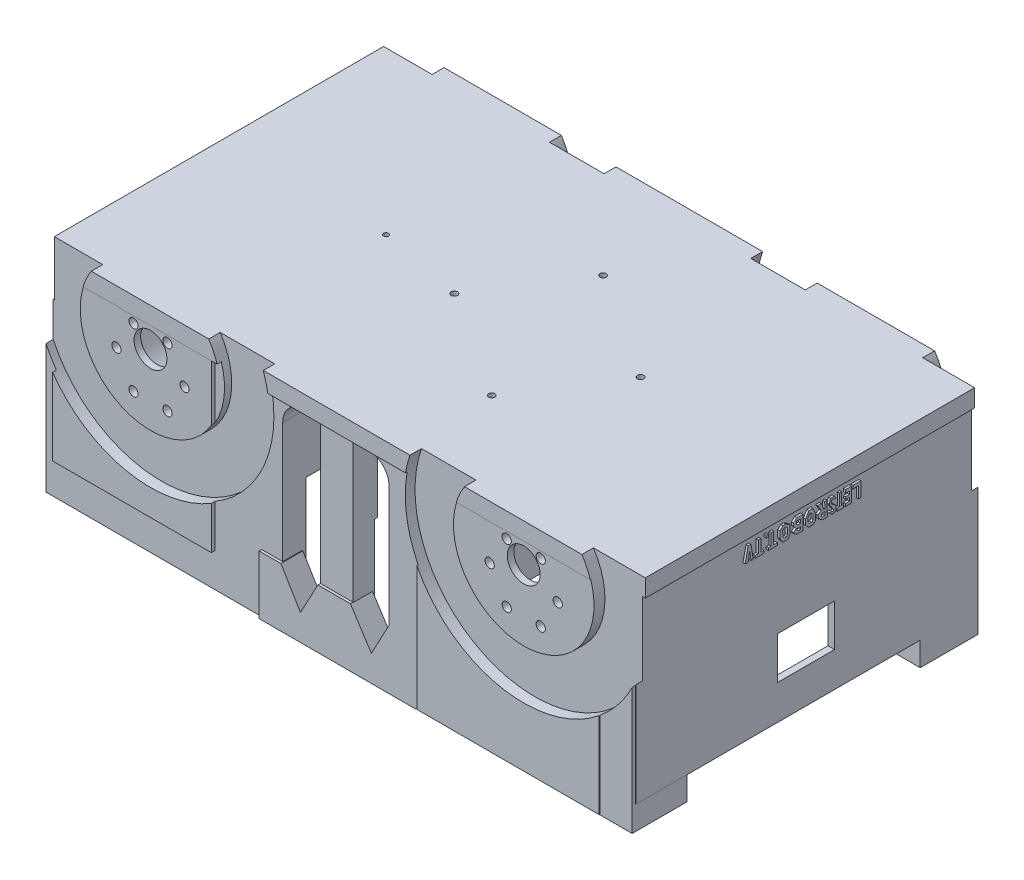
SolidWorks part; units mm, degrees
ref_plane "Front Plane" through (0, 0, 0) normal (0, 0, 1) x (1, 0, 0)
ref_plane "Top Plane" through (0, 0, 0) normal (0, 1, 0) x (1, 0, 0)
ref_plane "Right Plane" through (0, 0, 0) normal (1, 0, 0) x (0, 0, -1)
sketch "MotorHoldersSketch" plane through (0, 0, 0) normal (0, 0, 1) x (1, 0, 0)
  line L0 (0, 0) -> (170, 0) construction
  line L1 (0, 0) -> (0, 23.41) construction
  line L2 (170, 0) -> (170, 23.41) construction
  circle A0 centre (0, 0) radius 23.41
  circle A1 centre (170, 0) radius 23.41
ref_axis "MotorCenterAxis1" through (0, 0, 0) along (0, 0, 1)
ref_axis "MotorCenterAxis2" through (170, 0, 0) along (0, 0, 1)
extrude "MotorHolders" add sketch "MotorHoldersSketch" along normal blind 80 and the other way blind 80
sketch "Sketch3" plane through (0, 0, 0) normal (0, 0, 1) x (1, 0, 0)
  line L1 (1.9406, 21.133) -> (168.3435, 21.133)
  line L2 (1.9406, 21.133) -> (1.9406, 18.3155)
  line L3 (1.9406, 18.3155) -> (168.3435, 18.3155)
  line L4 (168.3435, 21.133) -> (168.3435, 18.3155)
sketch "Sketch4" plane through (0, 0, 0) normal (0, 1, 0) x (1, 0, 0)
  line L1 (221.2811, -76.3794) -> (-41.4939, -76.3794)
  line L2 (221.2811, -76.3794) -> (221.2811, 76.7331)
  line L3 (221.2811, 76.7331) -> (-41.4939, 76.7331)
  line L4 (-41.4939, -76.3794) -> (-41.4939, 76.7331)
extrude "Cut-Extrude1" cut sketch "Sketch4" against normal blind 26
ref_axis "Axis3" through (170, 0, 0) along (0, -1, 0)
sketch3d "ReferencePlanePosition"
  line L0 (170, 0, 0) -> (170, -34.8293, 0)
  line L1 (170, 0, 0) -> (170, -38.994, 0) construction
ref_plane "ReferencePlane" through (170, -34.8293, 0) normal (0, -1, 0) x (-1, 0, 0)
sketch "Sketch6" plane through (170, -34.8293, 0) normal (0, -1, 0) x (-1, 0, 0)
  line L1 (219.5858, 78.949) -> (112.1002, 78.949)
  line L2 (219.5858, 78.949) -> (219.5858, 65.5282)
  line L3 (219.5858, 65.5282) -> (112.1002, 65.5282)
  line L4 (112.1002, 78.949) -> (112.1002, 65.5282)
  line L5 (219.3147, -40.0209) -> (111.499, -40.0209)
  line L6 (219.3147, -40.0209) -> (219.3147, -78.2822)
  line L7 (219.3147, -78.2822) -> (111.499, -78.2822)
  line L8 (111.499, -40.0209) -> (111.499, -78.2822)
  line L9 (61.4891, 77.8627) -> (19.9904, 77.8627)
  line L10 (61.4891, 77.8627) -> (61.4891, 40.7512)
  line L11 (61.4891, 40.7512) -> (19.9904, 40.7512)
  line L12 (19.9904, 77.8627) -> (19.9904, 40.7512)
  line L13 (61.8484, -44.1716) -> (20.0852, -44.1716)
  line L14 (61.8484, -44.1716) -> (61.8484, -79.4437)
  line L15 (61.8484, -79.4437) -> (20.0852, -79.4437)
  line L16 (20.0852, -44.1716) -> (20.0852, -79.4437)
  line L17 (213.765, 73.0364) -> (192.9548, 73.0364)
  line L18 (213.765, 73.0364) -> (213.765, 71.0153)
  line L19 (213.765, 71.0153) -> (192.9548, 71.0153)
  line L20 (192.9548, 73.0364) -> (192.9548, 71.0153)
  line L21 (41.3552, 69.1777) -> (28.5109, 69.1777)
  line L22 (41.3552, 69.1777) -> (41.3552, 50.8413)
  line L23 (41.3552, 50.8413) -> (28.5109, 50.8413)
  line L24 (28.5109, 69.1777) -> (28.5109, 50.8413)
  line L25 (43.3068, -72.8101) -> (32.1723, -72.8101)
  line L26 (43.3068, -72.8101) -> (43.3068, -54.7747)
  line L27 (43.3068, -54.7747) -> (32.1723, -54.7747)
  line L28 (32.1723, -72.8101) -> (32.1723, -54.7747)
  line L29 (211.9411, -70.4881) -> (201.0982, -70.4881)
  line L30 (211.9411, -70.4881) -> (211.9411, -60.1404)
  line L31 (211.9411, -60.1404) -> (201.0982, -60.1404)
  line L32 (201.0982, -70.4881) -> (201.0982, -60.1404)
  line L33 (97.1795, 78.949) -> (79.4162, 78.949)
  line L34 (97.1795, 78.949) -> (97.1795, 67.7632)
  line L35 (97.1795, 67.7632) -> (79.4162, 67.7632)
  line L36 (79.4162, 78.949) -> (79.4162, 67.7632)
  line L37 (58.6711, 51.3198) -> (53.8697, 51.3198)
  line L38 (58.6711, 51.3198) -> (58.6711, 67.7632)
  line L39 (58.6711, 67.7632) -> (53.8697, 67.7632)
  line L40 (53.8697, 51.3198) -> (53.8697, 67.7632)
  line L41 (94.2281, -78.2822) -> (79.4162, -78.2822)
  line L42 (94.2281, -78.2822) -> (94.2281, -67.2515)
  line L43 (94.2281, -67.2515) -> (79.4162, -67.2515)
  line L44 (79.4162, -78.2822) -> (79.4162, -67.2515)
  line L45 (56.3648, -69.8638) -> (51.7107, -69.8638)
  line L46 (56.3648, -69.8638) -> (56.3648, -55.4273)
  line L47 (56.3648, -55.4273) -> (51.7107, -55.4273)
  line L48 (51.7107, -69.8638) -> (51.7107, -55.4273)
  line L49 (-20.7001, -79.4437) -> (-48.8506, -79.4437)
  line L50 (-20.7001, -79.4437) -> (-20.7001, -54.5097)
  line L51 (-20.7001, -54.5097) -> (-48.8506, -54.5097)
  line L52 (-48.8506, -79.4437) -> (-48.8506, -54.5097)
  line L53 (-18.3873, 77.8627) -> (-49.0581, 77.8627)
  line L54 (-18.3873, 77.8627) -> (-18.3873, 51.5325)
  line L55 (-18.3873, 51.5325) -> (-49.0581, 51.5325)
  line L56 (-49.0581, 77.8627) -> (-49.0581, 51.5325)
  line L57 (-41.8141, -72.8101) -> (-31.6362, -72.8101)
  line L58 (-41.8141, -72.8101) -> (-41.8141, -62.9794)
  line L59 (-41.8141, -62.9794) -> (-31.6362, -62.9794)
  line L60 (-31.6362, -72.8101) -> (-31.6362, -62.9794)
  line L61 (-31.6362, 69.1777) -> (-41.5347, 69.1777)
  line L62 (-31.6362, 69.1777) -> (-31.6362, 58.5421)
  line L63 (-31.6362, 58.5421) -> (-41.5347, 58.5421)
  line L64 (-41.5347, 69.1777) -> (-41.5347, 58.5421)
extrude "PowerBankHolders" add sketch "Sketch6" along normal blind 40 and the other way blind 59 separate body
sketch3d "3DSketch3"
  line L0 (170, 0, 0) -> (170, -64.5, 0) construction
ref_plane "Plane2" through (170, -64.5, 0) normal (0, -1, 0) x (-1, 0, 0)
sketch "Sketch7" plane through (170, -64.5, 0) normal (0, -1, 0) x (-1, 0, 0)
  line L1 (-9.5047, -80.801) -> (181.32, -80.801)
  line L2 (-9.5047, -80.801) -> (-9.5047, 73.8662)
  line L3 (-9.5047, 73.8662) -> (181.32, 73.8662)
  line L4 (181.32, -80.801) -> (181.32, 73.8662)
  line L5 (151.8712, -54.3972) -> (26.5361, -54.3972)
  line L6 (151.8712, -54.3972) -> (151.8712, 46.2413)
  line L7 (151.8712, 46.2413) -> (26.5361, 46.2413)
  line L8 (26.5361, -54.3972) -> (26.5361, 46.2413)
ref_point "Point1"
ref_point "Point2"
sketch3d "3DSketch11"
  line L0 (0, 0, -80) -> (170, 0, 80) construction
  point P4 (85, 0, 0)
sketch "MotorHolderExtrudeSketch" plane through (0, 0, 0) normal (0, 0, 1) x (1, 0, 0)
  circle A0 centre (170, 0) radius 20.415
  circle A1 centre (0, 0) radius 20.415
  circle A3 centre (0, 0) radius 23.41 construction
  circle A4 centre (170, 0) radius 23.41 construction
ref_point "TopOfMotors"
ref_plane "TangentToTopOfMotors" through (0, -20.415, 0) normal (0, 1, 0) x (1, 0, 0)
ref_axis "Axis4" through (85, 0, 0) along (0, -1, 0)
ref_plane "BottomOfPowerBankRegion" through (0, -20.425, 0) normal (0, 1, 0) x (1, 0, 0)
ref_point "CenterAtBottomOfPowerBank"
ref_plane "TopOfPowerBankPlane" through (0, -54.425, 0) normal (0, 1, 0) x (1, 0, 0)
sketch "Sketch13" plane through (0, -54.425, 0) normal (0, 1, 0) x (1, 0, 0)
  line L1 (-19.4498, 72.5454) -> (166.1636, 72.5454)
  line L2 (-19.4498, 72.5454) -> (-19.4498, -78.2051)
  line L3 (-19.4498, -78.2051) -> (166.1636, -78.2051)
  line L4 (166.1636, 72.5454) -> (166.1636, -78.2051)
  line L5 (19.3173, -49.583) -> (137.9607, -49.583)
  line L6 (19.3173, -49.583) -> (19.3173, -21.0549)
  line L7 (19.3173, -21.0549) -> (137.9607, -21.0549)
  line L8 (137.9607, -49.583) -> (137.9607, -21.0549)
  line L9 (19.3173, 56.6778) -> (137.9607, 56.6778)
  line L10 (19.3173, 56.6778) -> (19.3173, 36.3234)
  line L11 (19.3173, 36.3234) -> (137.9607, 36.3234)
  line L12 (137.9607, 56.6778) -> (137.9607, 36.3234)
  line L13 (19.3173, 18.3186) -> (137.9607, 18.3186)
  line L14 (19.3173, 18.3186) -> (19.3173, -7.3615)
  line L15 (19.3173, -7.3615) -> (137.9607, -7.3615)
  line L16 (137.9607, 18.3186) -> (137.9607, -7.3615)
sketch "Sketch15" plane through (150.0096, 0, 0) normal (1, 0, 0) x (0, 0, -1)
  line L1 (72.5313, -25.7765) -> (45.7099, -25.7765)
  line L2 (72.5313, -25.7765) -> (72.5313, -24.2242)
  line L3 (72.5313, -24.2242) -> (45.7099, -24.2242)
  line L4 (45.7099, -25.7765) -> (45.7099, -24.2242)
ref_plane "Plane6" through (0, 0, 0) normal (0, 0, 1) x (1, 0, 0)
sketch "MotorGeometry1" plane through (0, 0, 0) normal (0, 0, 1) x (1, 0, 0)
  line L0 (170, 0) -> (170, -13.42)
  line L1 (170, 0) -> (170, -34.8293) construction
  line L2 (170, -13.42) -> (162.25, -13.42) construction
  line L3 (170, -13.42) -> (177.75, -13.42) construction
  line L4 (170, -13.42) -> (170, 7) construction
  line L5 (170, 0) -> (185.5, 0) construction
  line L6 (170, 0) -> (154.5, 0) construction
  line L7 (170, 0) -> (170, 13.42) construction
  line L8 (170, 0) -> (170, 23.41) construction
  line L9 (170, 13.42) -> (177.75, 13.42) construction
  line L10 (170, 13.42) -> (162.25, 13.42)
ref_axis "BoltAxisA" through (185.5, 0, 0) along (0, 0, 1)
ref_axis "BoltAxisB" through (177.75, -13.42, 0) along (0, 0, 1)
ref_axis "BoltAxisC" through (162.25, -13.42, 0) along (0, 0, 1)
ref_axis "BoltAxisD" through (154.5, 0, 0) along (0, 0, 1)
ref_axis "BoltAxisE" through (162.25, 13.42, 0) along (0, 0, 1)
ref_axis "BoltAxisF" through (177.75, 13.42, 0) along (0, 0, 1)
ref_point "Point6"
ref_point "Point7"
ref_point "Point8"
ref_point "Point9"
ref_point "Point10"
ref_point "Point11"
ref_point "Point12"
ref_point "Point13"
ref_point "Point14"
ref_point "Point15"
ref_point "Point16"
ref_point "Point17"
ref_plane "Plane7" through (0, 0, 0) normal (0, 0, 1) x (1, 0, 0)
sketch "MotorGeometry2" plane through (0, 0, 0) normal (0, 0, 1) x (1, 0, 0)
  line L0 (0, 0) -> (0, -13.42) construction
  line L1 (0, -13.42) -> (7.75, -13.42) construction
  line L2 (0, -13.42) -> (-7.75, -13.42) construction
  line L3 (0, 0) -> (0, 13.42)
  line L4 (0, -13.42) -> (0, 7) construction
  line L5 (0, 13.42) -> (7.75, 13.42) construction
  line L6 (0, 13.42) -> (-7.75, 13.42) construction
  line L7 (0, 0) -> (15.5, 0) construction
  line L8 (0, 0) -> (-15.5, 0) construction
  line L9 (0, 0) -> (0, 23.41) construction
ref_axis "Axis11" through (15.5, 0, 0) along (0, 0, 1)
ref_axis "Axis12" through (7.75, 13.42, 0) along (0, 0, 1)
ref_axis "Axis13" through (-7.75, 13.42, 0) along (0, 0, 1)
ref_axis "Axis14" through (-15.5, 0, 0) along (0, 0, 1)
ref_axis "Axis15" through (-7.75, -13.42, 0) along (0, 0, 1)
ref_axis "Axis16" through (7.75, -13.42, 0) along (0, 0, 1)
ref_point "Point18"
ref_point "Point19"
ref_point "Point20"
ref_point "Point21"
ref_point "Point22"
ref_point "Point23"
ref_point "Point24"
ref_point "Point25"
ref_point "Point26"
ref_point "Point27"
ref_point "Point28"
ref_point "Point29"
ref_plane "BottomPlane" through (0, 19.575, 0) normal (0, 1, 0) x (1, 0, 0)
ref_axis "OutputShaftReference1" through (0, 7, 0) along (0, 0, 1)
ref_point "Point35"
ref_axis "OutputShaftReference2" through (170, 7, 0) along (0, 0, 1)
sketch "Sketch21" plane through (0, 19.575, 0) normal (0, 1, 0) x (1, 0, 0)
  line L0 (219.6842, -79.5488) -> (-50.341, -79.5488) construction
  line L1 (-50.341, -79.5488) -> (-50.341, 79.7899) construction
  line L2 (-50.341, 79.7899) -> (219.6842, 79.7899) construction
  line L3 (219.6842, 79.7899) -> (219.6842, -79.5488) construction
  circle A0 centre (85, 0) radius 156.3953
extrude "BottomPlate" add sketch "Sketch21" along normal blind 5 and the other way blind 3
ref_plane "HoleReferencePlane1" through (0, 0, 80) normal (0, 0, 1) x (1, 0, 0)
ref_point "OutputShaftPosition3"
ref_point "OutputShaftPosition1"
sketch "Sketch23" plane through (0, 0, 80) normal (0, 0, 1) x (1, 0, 0)
  line L1 (27.7411, -59.3229) -> (-44.5901, -59.3229)
  line L2 (27.7411, -59.3229) -> (27.7411, 21.8402)
  line L3 (27.7411, 21.8402) -> (-44.5901, 21.8402)
  line L4 (-44.5901, -59.3229) -> (-44.5901, 21.8402)
  line L5 (121.3218, 21.8402) -> (204.258, 21.8402)
  line L6 (121.3218, 21.8402) -> (121.3218, -74.371)
  line L7 (121.3218, -74.371) -> (204.258, -74.371)
  line L8 (204.258, 21.8402) -> (204.258, -74.371)
extrude "MotorMountingSupport1" add sketch "Sketch23" against normal blind 6
ref_plane "HoleReferencePlane2" through (0, 0, -80) normal (0, 0, -1) x (-1, 0, 0)
ref_point "OutputShaftPosition4"
ref_point "OutputShaftPosition2"
sketch "Sketch24" plane through (0, 0, -80) normal (0, 0, -1) x (-1, 0, 0)
  line L1 (-202.1905, -75.2023) -> (-123.8485, -75.2023)
  line L2 (-202.1905, -75.2023) -> (-202.1905, 19.2374)
  line L3 (-202.1905, 19.2374) -> (-123.8485, 19.2374)
  line L4 (-123.8485, -75.2023) -> (-123.8485, 19.2374)
  line L5 (-24.3642, -64.1521) -> (29.5505, -64.1521)
  line L6 (-24.3642, -64.1521) -> (-24.3642, 22.5226)
  line L7 (-24.3642, 22.5226) -> (29.5505, 22.5226)
  line L8 (29.5505, -64.1521) -> (29.5505, 22.5226)
extrude "MotorMountingSuppor2" add sketch "Sketch24" against normal blind 6
sketch "Sketch17" plane through (0, 0, 80) normal (0, 0, 1) x (1, 0, 0)
  circle A0 centre (185.5, 0) radius 2.1
  circle A1 centre (177.75, -13.42) radius 2.1
  circle A2 centre (162.25, -13.42) radius 2.1
  circle A3 centre (154.5, 0) radius 2.1
  circle A4 centre (162.25, 13.42) radius 2.1
  circle A5 centre (177.75, 13.42) radius 2.1
  circle A6 centre (170, 7) radius 7.5
extrude "MotorHoles1" cut sketch "Sketch17" against normal blind 31.5
sketch "Sketch19" plane through (0, 0, -80) normal (0, 0, -1) x (-1, 0, 0)
  circle A0 centre (-185.5, 0) radius 2.1
  circle A1 centre (-177.75, -13.42) radius 2.1
  circle A2 centre (-162.25, -13.42) radius 2.1
  circle A3 centre (-154.5, 0) radius 2.1
  circle A4 centre (-162.25, 13.42) radius 2.1
  circle A5 centre (-177.75, 13.42) radius 2.1
  circle A6 centre (-170, 7) radius 7.5
sketch "BoltHolesSketch3" plane through (0, 0, 80) normal (0, 0, 1) x (1, 0, 0)
  circle A0 centre (7.75, -13.42) radius 2.1
  circle A1 centre (15.5, 0) radius 2.1
  circle A2 centre (7.75, 13.42) radius 2.1
  circle A3 centre (-7.75, 13.42) radius 2.1
  circle A4 centre (-15.5, 0) radius 2.1
  circle A5 centre (-7.75, -13.42) radius 2.1
  circle A6 centre (0, 7) radius 7.5
extrude "Cut-Extrude4" cut sketch "Sketch19" against normal blind 30
extrude "MotorHoles3" cut sketch "BoltHolesSketch3" against normal blind 31.5
sketch "BoltHolesSketch4" plane through (0, 0, -80) normal (0, 0, -1) x (-1, 0, 0)
  circle A0 centre (-15.5, 0) radius 2.1
  circle A1 centre (-7.75, 13.42) radius 2.1
  circle A2 centre (7.75, 13.42) radius 2.1
  circle A3 centre (15.5, 0) radius 2.1
  circle A4 centre (7.75, -13.42) radius 2.1
  circle A5 centre (-7.75, -13.42) radius 2.1
  circle A6 centre (0, 7) radius 7.5
extrude "MotorHoles4" cut sketch "BoltHolesSketch4" against normal blind 15
ref_plane "Front" through (219.0581, 0, 0) normal (1, 0, 0) x (0, 0, -1)
sketch "Sketch29" plane through (219.0581, 0, 0) normal (1, 0, 0) x (0, 0, -1)
  line L1 (76.6955, -63.9254) -> (-77.9397, -63.9254)
  line L2 (76.6955, -63.9254) -> (76.6955, 20.2062)
  line L3 (76.6955, 20.2062) -> (-77.9397, 20.2062)
  line L4 (-77.9397, -63.9254) -> (-77.9397, 20.2062)
  line L5 (-13.4507, -48.1531) -> (12.5493, -48.1531)
  line L6 (-13.4507, -48.1531) -> (-13.4507, -28.9404)
  line L7 (-13.4507, -28.9404) -> (12.5493, -28.9404)
  line L8 (12.5493, -48.1531) -> (12.5493, -28.9404)
extrude "Boss-Extrude8" add sketch "Sketch29" against normal blind 3
ref_plane "RaspberryPiBasePlane" through (0, 16.575, 0) normal (0, -1, 0) x (-1, 0, 0)
sketch "Sketch27" plane through (0, 16.575, 0) normal (0, -1, 0) x (-1, 0, 0)
  line L1 (31.6337, 64.5517) -> (-194.8264, 64.5517)
  line L2 (31.6337, 64.5517) -> (31.6337, -65.4335)
  line L3 (31.6337, -65.4335) -> (-194.8264, -65.4335)
  line L4 (-194.8264, 64.5517) -> (-194.8264, -65.4335)
extrude "Boss-Extrude6" add sketch "Sketch27" against normal blind 3
ref_plane "Plane12" through (0, -74.8293, 0) normal (0, -1, 0) x (-1, 0, 0)
sketch "Sketch28" plane through (0, -74.8293, 0) normal (0, -1, 0) x (-1, 0, 0)
  line L1 (-189.3897, -97.3973) -> (-123.0026, -97.3973)
  line L2 (-189.3897, -97.3973) -> (-189.3897, 96.7192)
  line L3 (-189.3897, 96.7192) -> (-123.0026, 96.7192)
  line L4 (-123.0026, -97.3973) -> (-123.0026, 96.7192)
sketch "Sketch40" plane through (0, 16.575, 0) normal (0, -1, 0) x (1, 0, 0)
  line L1 (-49.5858, -65.5282) -> (-15.7443, -65.5282)
  line L2 (-49.5858, -65.5282) -> (-49.5858, -33.9964)
  line L3 (-49.5858, -33.9964) -> (-15.7443, -33.9964)
  line L4 (-15.7443, -65.5282) -> (-15.7443, -33.9964)
extrude "Boss-Extrude11" add sketch "Sketch40" along normal blind 40
fillet "Fillet2" radius 15 1 edges at (-33.0588, 16.575, -33.9964) type face fillet first side face at (-28.7089, -2.1691, -33.9964) second side face at (85, 16.575, 156.3953)
fillet "Fillet3" radius 15 1 edges at (-32.6651, -23.425, -65.5282) type face fillet first side face at (-5.65, -13.42, -65.5282) second side face at (-32.6651, -23.425, -49.7623)
sketch "Sketch11" plane through (0, -20.425, 0) normal (0, 1, 0) x (1, 0, 0)
  line L0 (-34.2162, 4.2922) -> (204.2162, -4.2922) construction
  line L5 (-34.2162, -64.7581) -> (-34.2162, 73.3425)
  line L6 (204.2162, 63.611) -> (204.2162, -72.1954)
  line L7 (204.2162, -72.1954) -> (-34.2162, -64.7581)
  line L8 (204.2162, 63.611) -> (-34.2162, 73.3425)
  circle A0 centre (85, 0) radius 104 construction
extrude "PowerBankCut" cut sketch "Sketch11" against normal up to surface (54.4043 mm away) up to face at (204.7754, -74.8293, 66.9767)
extrude "MotorHolderCut" cut sketch "MotorHolderExtrudeSketch" against normal blind 77 and the other way blind 77
sketch "Sketch31" plane through (219.0581, 0, 0) normal (1, 0, 0) x (0, 0, -1)
  line L0 (-11.9853, 13.4398) -> (-13.3624, 12.0627)
  line L1 (-13.3624, 12.0627) -> (-13.3624, 8.9452)
  line L2 (-11.9853, 6.9748) -> (-13.3624, 8.9452)
  line L3 (23.5583, 6.7877) -> (23.5583, 13.4398)
  line L4 (23.5583, 13.4398) -> (19.9736, 13.4398)
  line L5 (19.9736, 13.4398) -> (19.9736, 12.0236)
  line L6 (19.9736, 12.0236) -> (22.4953, 12.0236)
  line L7 (22.4953, 12.0236) -> (22.4953, 6.7877)
  line L8 (23.5583, 6.7877) -> (22.4953, 6.7877)
  line L9 (19.3464, 13.4398) -> (19.3464, 6.7877)
  line L10 (19.3464, 6.7877) -> (16.5174, 6.7877)
  line L11 (16.5174, 6.7877) -> (16.5174, 7.9482)
  line L12 (16.5174, 7.9482) -> (18.3741, 7.9482)
  line L13 (18.3741, 7.9482) -> (18.3741, 9.5315)
  line L14 (18.3741, 9.5315) -> (16.5174, 9.5315)
  line L15 (16.5174, 9.5315) -> (16.5174, 10.6274)
  line L16 (16.5174, 10.6274) -> (18.3741, 10.6274)
  line L17 (18.3741, 10.6274) -> (18.3741, 12.0236)
  line L18 (18.3741, 12.0236) -> (16.5174, 12.0236)
  line L19 (16.5174, 12.0236) -> (16.5174, 13.4398)
  line L20 (19.3464, 13.4398) -> (16.5174, 13.4398)
  line L21 (15.6231, 6.7877) -> (15.6231, 7.9482)
  line L22 (15.6231, 6.7877) -> (12.7162, 6.7877)
  line L23 (12.7162, 6.7877) -> (12.7162, 7.9482)
  line L24 (12.7162, 7.9482) -> (13.819, 7.9482)
  line L25 (13.819, 7.9482) -> (13.819, 13.4398)
  line L26 (13.819, 13.4398) -> (14.771, 13.4398)
  line L27 (14.771, 13.4398) -> (14.771, 7.9482)
  line L28 (15.6231, 7.9482) -> (14.771, 7.9482)
  line L29 (9.0737, 7.9482) -> (10.2342, 6.7877)
  line L30 (10.2342, 6.7877) -> (11.2446, 6.7877)
  line L31 (11.2446, 6.7877) -> (12.156, 7.699)
  line L32 (12.156, 7.699) -> (12.156, 9.5315)
  line L33 (12.156, 9.5315) -> (10.2342, 10.8736)
  line L34 (9.0737, 7.9482) -> (10.2342, 7.9482)
  line L35 (10.2342, 7.9482) -> (10.6704, 7.699)
  line L36 (10.6704, 7.699) -> (11.2446, 8.0737)
  line L37 (11.2446, 8.0737) -> (9.0737, 11.4008)
  line L38 (9.0737, 11.4008) -> (9.6875, 13.4398)
  line L39 (9.6875, 13.4398) -> (11.4814, 13.4398)
  line L40 (11.4814, 13.4398) -> (12.156, 12.3409)
  line L41 (12.156, 12.3409) -> (11.2446, 12.3409)
  line L42 (11.2446, 12.3409) -> (10.6704, 12.772)
  line L43 (10.6704, 12.772) -> (10.1086, 12.0236)
  line L44 (10.1086, 12.0236) -> (10.2342, 10.8736)
  line L45 (-20.664, 6.9748) -> (-20.664, 8.0737)
  line L46 (-18.6605, 13.4398) -> (-19.6346, 13.4398)
  line L47 (-18.6605, 13.4398) -> (-18.6605, 12.3409)
  line L48 (-18.6605, 12.3409) -> (-19.6346, 12.3409)
  line L49 (-19.6346, 13.4398) -> (-19.6346, 12.3409)
  line L50 (-20.664, 8.0737) -> (-22.0801, 8.0737)
  line L51 (-20.664, 6.9748) -> (-24.6188, 6.9748)
  line L52 (-24.6188, 6.9748) -> (-24.6188, 8.0737)
  line L53 (-24.6188, 8.0737) -> (-23.2262, 8.0737)
  line L54 (-22.0801, 8.0737) -> (-22.0801, 13.4398)
  line L55 (-22.0801, 13.4398) -> (-23.2262, 13.4398)
  line L56 (8.0122, 13.4398) -> (8.253, 6.7877)
  line L57 (8.253, 6.7877) -> (6.0128, 6.7877)
  line L58 (6.0128, 6.7877) -> (4.2685, 7.9482)
  line L59 (4.2685, 7.9482) -> (3.8991, 9.7863)
  line L60 (3.8991, 9.7863) -> (5.5426, 10.6274)
  line L61 (5.5426, 10.6274) -> (3.8991, 13.4398)
  line L62 (3.8991, 13.4398) -> (5.5426, 13.4398)
  line L63 (5.5426, 13.4398) -> (6.5701, 10.6274)
  line L64 (6.5701, 10.6274) -> (7.1329, 10.6274)
  line L65 (7.1329, 10.6274) -> (7.0311, 13.4398)
  line L66 (7.0311, 13.4398) -> (8.0122, 13.4398)
  line L67 (1.6684, 13.4398) -> (-0.1827, 13.4398)
  line L68 (-0.1827, 13.4398) -> (-1.6538, 10.8736)
  line L69 (-1.6538, 10.8736) -> (-1.6538, 8.4246)
  line L70 (-1.6538, 8.4246) -> (-0.1827, 6.9535)
  line L71 (-0.1827, 6.9535) -> (1.6684, 6.9535)
  line L72 (1.6684, 6.9535) -> (2.9495, 8.2346)
  line L73 (2.9495, 8.2346) -> (2.9495, 10.6274)
  line L74 (2.9495, 10.6274) -> (1.6684, 13.4398)
  line L75 (-2.9468, 6.9535) -> (-2.9468, 13.4398)
  line L76 (-2.9468, 13.4398) -> (-5.696, 13.4398)
  line L77 (-5.696, 13.4398) -> (-7.1123, 12.0236)
  line L78 (-7.1123, 12.0236) -> (-7.1123, 10.6274)
  line L79 (-7.1123, 10.6274) -> (-5.9341, 9.4492)
  line L80 (-5.9341, 9.4492) -> (-7.1123, 8.2711)
  line L81 (-7.1123, 8.2711) -> (-7.1123, 7.9482)
  line L82 (-7.1123, 7.9482) -> (-5.696, 6.9535)
  line L83 (-5.696, 6.9535) -> (-2.9468, 6.9535)
  line L84 (-9.9534, 6.9535) -> (-8.8331, 8.0737)
  line L85 (-8.8331, 8.0737) -> (-8.8331, 12.3409)
  line L86 (-8.8331, 12.3409) -> (-10.7011, 13.4398)
  line L87 (-10.7011, 13.4398) -> (-11.9853, 13.4398)
  line L88 (-23.2262, 13.4398) -> (-23.2262, 8.0737)
  line L89 (-25.5187, 6.9748) -> (-26.5366, 13.4398)
  line L90 (-26.5366, 13.4398) -> (-27.8126, 13.4398)
  line L91 (-11.9853, 6.9748) -> (-9.9534, 6.9535)
  line L92 (-14.5404, 6.9748) -> (-18.6605, 6.9748)
  line L93 (-18.6605, 6.9748) -> (-18.6605, 8.0737)
  line L94 (-18.6605, 8.0737) -> (-17.3325, 8.0737)
  line L95 (-17.3325, 8.0737) -> (-17.3325, 13.4398)
  line L96 (-17.3325, 13.4398) -> (-16.1754, 13.4398)
  line L97 (-16.1754, 13.4398) -> (-16.1754, 8.0737)
  line L98 (-16.1754, 8.0737) -> (-14.5404, 8.0737)
  line L99 (-14.5404, 8.0737) -> (-14.5404, 6.9748)
  line L100 (1.1066, 8.2346) -> (1.8172, 8.9452)
  line L101 (1.8172, 8.9452) -> (1.8172, 11.1371)
  line L102 (1.8172, 11.1371) -> (0.8255, 12.1288)
  line L103 (0.8255, 12.1288) -> (0.2118, 12.1288)
  line L104 (0.2118, 12.1288) -> (-0.525, 11.1371)
  line L105 (-0.525, 11.1371) -> (-0.6294, 9.2253)
  line L106 (-0.6294, 9.2253) -> (0.0159, 8.2739)
  line L107 (0.0159, 8.2739) -> (1.1066, 8.2346)
  line L108 (-4.0608, 9.2253) -> (-5.4172, 9.2253)
  line L109 (-5.4172, 9.2253) -> (-5.696, 8.4246)
  line L110 (-5.696, 8.4246) -> (-4.9992, 7.9482)
  line L111 (-4.9992, 7.9482) -> (-4.0608, 7.9482)
  line L112 (-4.0608, 7.9482) -> (-4.0608, 9.2253)
  line L113 (-3.8961, 10.3794) -> (-3.8961, 12.1288)
  line L114 (-3.8961, 12.1288) -> (-5.5739, 12.3409)
  line L115 (-5.5739, 12.3409) -> (-6.0661, 11.2541)
  line L116 (-6.0661, 11.2541) -> (-5.257, 10.3794)
  line L117 (-5.257, 10.3794) -> (-3.8961, 10.3794)
  line L118 (-10.3458, 8.2739) -> (-9.9534, 8.9452)
  line L119 (-9.9534, 8.9452) -> (-9.9534, 11.8216)
  line L120 (-9.9534, 11.8216) -> (-10.9018, 12.3409)
  line L121 (-10.9018, 12.3409) -> (-11.4919, 12.3409)
  line L122 (-11.4919, 12.3409) -> (-12.1481, 11.6848)
  line L123 (-12.1481, 11.6848) -> (-11.9853, 8.9452)
  line L124 (-11.9853, 8.9452) -> (-11.4919, 8.2739)
  line L125 (-11.4919, 8.2739) -> (-10.3458, 8.2739)
  line L126 (7.1329, 7.9482) -> (7.1329, 9.5315)
  line L127 (7.1329, 9.5315) -> (6.0128, 9.5315)
  line L128 (6.0128, 9.5315) -> (5.5426, 9.0613)
  line L129 (5.5426, 9.0613) -> (5.5426, 8.4246)
  line L130 (5.5426, 8.4246) -> (6.0932, 7.874)
  line L131 (6.0932, 7.874) -> (7.1329, 7.9482)
  line L132 (-27.8126, 13.4398) -> (-29.1855, 6.9748)
  line L133 (-29.1855, 6.9748) -> (-27.8126, 6.9748)
  line L134 (-27.8126, 6.9748) -> (-27.1746, 11.2541)
  line L135 (-27.1746, 11.2541) -> (-26.5008, 6.9748)
  line L136 (-26.5008, 6.9748) -> (-25.5187, 6.9748)
extrude "Label" add sketch "Sketch31" along normal blind 1
sketch "Sketch32" plane through (0, 19.575, 0) normal (0, 1, 0) x (1, 0, 0)
  line L1 (-48.8137, 80.4301) -> (220.392, 80.4301)
  line L2 (-48.8137, 80.4301) -> (-48.8137, -80.215)
  line L3 (-48.8137, -80.215) -> (220.392, -80.215)
  line L4 (220.392, 80.4301) -> (220.392, -80.215)
  line L5 (283.5566, -218.7268) -> (-136.4889, -218.7268)
  line L8 (-136.4889, -218.7268) -> (-136.4889, 206.3198)
  line L10 (283.5566, 206.3198) -> (283.5566, -218.7268)
  line L13 (283.5566, 206.3198) -> (-136.4889, 206.3198)
extrude "BaseDefiningCut" cut sketch "Sketch32" along normal blind 20 and the other way blind 20
sketch "Sketch39" plane through (0, 16.575, 0) normal (0, -1, 0) x (1, 0, 0)
  line L1 (-48.8137, -65.5282) -> (-16.0867, -65.5282)
  line L2 (-48.8137, -65.5282) -> (-48.8137, -46.28)
  line L3 (-48.8137, -46.28) -> (-16.0867, -46.28)
  line L4 (-16.0867, -65.5282) -> (-16.0867, -46.28)
sketch "Sketch35" plane through (0, 0, -80.4301) normal (0, 0, -1) x (-1, 0, 0)
  line L0 (69.0502, 16.3777) -> (-36.4474, 27.6206)
  line L1 (-36.4474, 27.6206) -> (71.6404, 26.1593)
  line L2 (69.0502, 16.3777) -> (71.6404, 26.1593)
  line L3 (-223.8844, 30.8145) -> (-223.8844, 17.5678)
  line L4 (-223.8844, 17.5678) -> (-116.0163, 30.8145)
  line L5 (-116.0163, 30.8145) -> (-223.8844, 30.8145)
sketch "Sketch36" plane through (-49.3147, 0, 0) normal (-1, 0, 0) x (0, 0, 1)
  line L0 (40.0209, -74.8293) -> (40.0209, -38.3689) construction
  line L1 (49.3822, -38.3689) -> (78.2822, -38.3689) construction
  line L2 (40.0209, -38.3689) -> (40.0209, -74.8293) construction
  line L3 (78.2822, -0.425) -> (78.2822, -74.8293) construction
  circle A1 centre (49.3822, -38.3689) radius 7.7902
extrude "Cut-Extrude6" cut sketch "Sketch36" against normal blind 40
sketch "Sketch37" plane through (0, -20.425, 0) normal (0, -1, 0) x (1, 0, 0)
  line L1 (144.416, -35.6729) -> (89.0759, -35.6729)
  line L2 (144.416, -35.6729) -> (144.416, -65.4438)
  line L3 (144.416, -65.4438) -> (89.0759, -65.4438)
  line L4 (89.0759, -35.6729) -> (89.0759, -65.4438)
extrude "Cut-Extrude7" cut sketch "Sketch37" against normal blind 36
sketch "Sketch38" plane through (0, 16.575, 0) normal (0, -1, 0) x (1, 0, 0)
  line L0 (25.9964, 80.215) -> (25.9964, -1.3165) construction
  line L1 (-48.8137, 80.215) -> (219.2574, 80.215) construction
  circle A0 centre (25.9964, -1.3165) radius 1.1452
extrude "Cut-Extrude8" cut sketch "Sketch38" against normal blind 10
sketch "Sketch41" plane through (0, 0, 80) normal (0, 0, 1) x (1, 0, 0)
  circle A0 centre (0, 7) radius 32
  circle A1 centre (0, 7) radius 54.5
extrude "SpaceForWheel1" cut sketch "Sketch41" against normal blind 5 and the other way blind 10
sketch "Sketch42" plane through (0, 0, 80) normal (0, 0, 1) x (1, 0, 0)
  circle A0 centre (170, 7) radius 32
  circle A1 centre (170, 7) radius 54.5
extrude "Cut-Extrude10" cut sketch "Sketch42" against normal blind 5 and the other way blind 10
sketch "Sketch43" plane through (0, 0, -80) normal (0, 0, -1) x (-1, 0, 0)
  circle A0 centre (-170, 7) radius 32
  circle A1 centre (-170, 7) radius 54.5
extrude "Cut-Extrude11" cut sketch "Sketch43" against normal blind 5 and the other way blind 10
sketch "Sketch44" plane through (0, 0, -80) normal (0, 0, -1) x (-1, 0, 0)
  circle A0 centre (0, 7) radius 32
  circle A1 centre (0, 7) radius 54.5
extrude "Cut-Extrude12" cut sketch "Sketch44" against normal blind 5 and the other way blind 10
sketch "Sketch45" plane through (-48.8137, 0, 0) normal (-1, 0, 0) x (0, 0, 1)
  line L0 (-75, 24.575) -> (75, 24.575) construction
  line L1 (-72.1063, 24.575) -> (42.0312, 24.575)
  line L2 (-72.1063, 24.575) -> (-72.1063, -74.1222)
  line L3 (-72.1063, -74.1222) -> (42.0312, -74.1222)
  line L4 (42.0312, 24.575) -> (42.0312, -74.1222)
extrude "BackPlate" add sketch "Sketch45" against normal blind 2
sketch "Sketch46" plane through (0, -74.8293, 0) normal (0, -1, 0) x (1, 0, 0)
  line L1 (97.1427, -74.9256) -> (213.5256, -74.9256)
  line L2 (97.1427, -74.9256) -> (97.1427, -71.5234)
  line L3 (97.1427, -71.5234) -> (213.5256, -71.5234)
  line L4 (213.5256, -74.9256) -> (213.5256, -71.5234)
  line L5 (97.1427, 72.8226) -> (213.5256, 72.8226)
  line L6 (97.1427, 72.8226) -> (97.1427, 77.4687)
  line L7 (97.1427, 77.4687) -> (213.5256, 77.4687)
  line L8 (213.5256, 72.8226) -> (213.5256, 77.4687)
fillet "Fillet8" radius 10 1 edges at (57.8998, 16.575, -72.2386) type face fillet first side face at (57.8998, -26.2264, -71.3533) second side face at (25.9964, 16.575, -2.4617)
fillet "Fillet9" radius 10 1 edges at (108.5109, 16.575, -59.3069) type face fillet first side face at (108.5109, -15.7761, -62.8937) second side face at (25.9964, 16.575, -2.4617)
fillet "Fillet10" radius 10 1 edges at (108.1516, 16.575, 61.8076) type face fillet first side face at (108.1516, -26.2264, 64.2714) second side face at (25.9964, 16.575, -2.4617)
sketch "Sketch49" plane through (0, 0, 80) normal (0, 0, 1) x (1, 0, 0)
  line L0 (27.7411, -8.9509) -> (27.7411, 16.575) construction
  circle A0 centre (27.7411, 12.953) radius 3.5831
fillet "Fillet11" radius 10 1 edges at (58.501, 16.575, 59.1515) type face fillet first side face at (58.501, -26.2264, 61.9844) second side face at (25.9964, 16.575, -2.4617)
sketch "Sketch50" plane through (0, -74.8293, 0) normal (0, -1, 0) x (1, 0, 0)
  line L1 (-49.3147, 40.0209) -> (-40.7689, 40.0209)
  line L2 (-49.3147, 40.0209) -> (-49.3147, 52.7795)
  line L3 (-49.3147, 52.7795) -> (-40.7689, 52.7795)
  line L4 (-40.7689, 40.0209) -> (-40.7689, 52.7795)
  line L5 (-49.5858, -65.5282) -> (-35.8777, -65.5282)
  line L6 (-49.5858, -65.5282) -> (-49.5858, -77.7316)
  line L7 (-49.5858, -77.7316) -> (-35.8777, -77.7316)
  line L8 (-35.8777, -65.5282) -> (-35.8777, -77.7316)
sketch "Sketch51" plane through (0, 0, 79.4437) normal (0, 0, 1) x (1, 0, 0)
  line L0 (108.1516, -47.9804) -> (100.047, -63.1792)
  line L1 (108.1516, 6.575) -> (108.1516, -74.8293) construction
  line L2 (100.047, -63.1792) -> (90.5163, -48.3368)
  line L3 (90.5163, -48.3368) -> (75.6762, -48.3368)
  line L4 (75.6762, -48.3368) -> (67.7615, -63.1792)
  line L5 (67.7615, -63.1792) -> (58.8398, -48.3368)
  line L6 (58.8398, -48.3368) -> (48.9291, -48.3368)
  line L7 (48.9291, -48.3368) -> (48.9291, -75.0407)
  line L8 (48.9291, -75.0407) -> (120.2514, -75.0407)
  line L9 (120.2514, -75.0407) -> (120.2514, -47.9804)
  line L10 (120.2514, -47.9804) -> (108.1516, -47.9804)
extrude "Boss-Extrude12" add sketch "Sketch51" against normal blind 10
sketch "Sketch53" plane through (0, 0, -77.8627) normal (0, 0, -1) x (-1, 0, 0)
  line L1 (-57.7992, -55.7616) -> (-64.6668, -65.1072)
  line L2 (-64.6668, -65.1072) -> (-72.7541, -55.7616)
  line L3 (-72.7541, -55.7616) -> (-90.6554, -55.7616)
  line L4 (-90.6554, -55.7616) -> (-98.6681, -65.1072)
  line L5 (-98.6681, -65.1072) -> (-108.5109, -55.7616)
  line L6 (-108.5109, 6.575) -> (-108.5109, -74.8293) construction
  line L7 (-108.5109, -55.7616) -> (-123.8485, -55.7616)
  line L8 (-123.8485, -21.9878) -> (-123.8485, -74.8293) construction
  line L9 (-123.8485, -55.7616) -> (-123.8485, -74.8293)
  line L10 (-123.8485, -74.8293) -> (-52.4383, -74.8293)
  line L11 (-52.4383, -74.8293) -> (-52.4383, -55.7616)
  line L12 (-52.4383, -55.7616) -> (-57.7992, -55.7616)
extrude "Boss-Extrude13" add sketch "Sketch53" against normal blind 9
sketch "HolesForRasPiMounting" plane through (0, 16.575, 0) normal (0, -1, 0) x (1, 0, 0)
  circle A0 centre (91.4678, -34.696) radius 1.4146
  circle A1 centre (64.7805, 6.3989) radius 1.4536
  circle A2 centre (140.1107, -3.1069) radius 1.4303
  circle A3 centre (113.4234, 37.9879) radius 1.4064
extrude "Cut-Extrude13" cut sketch "HolesForRasPiMounting" against normal through all
